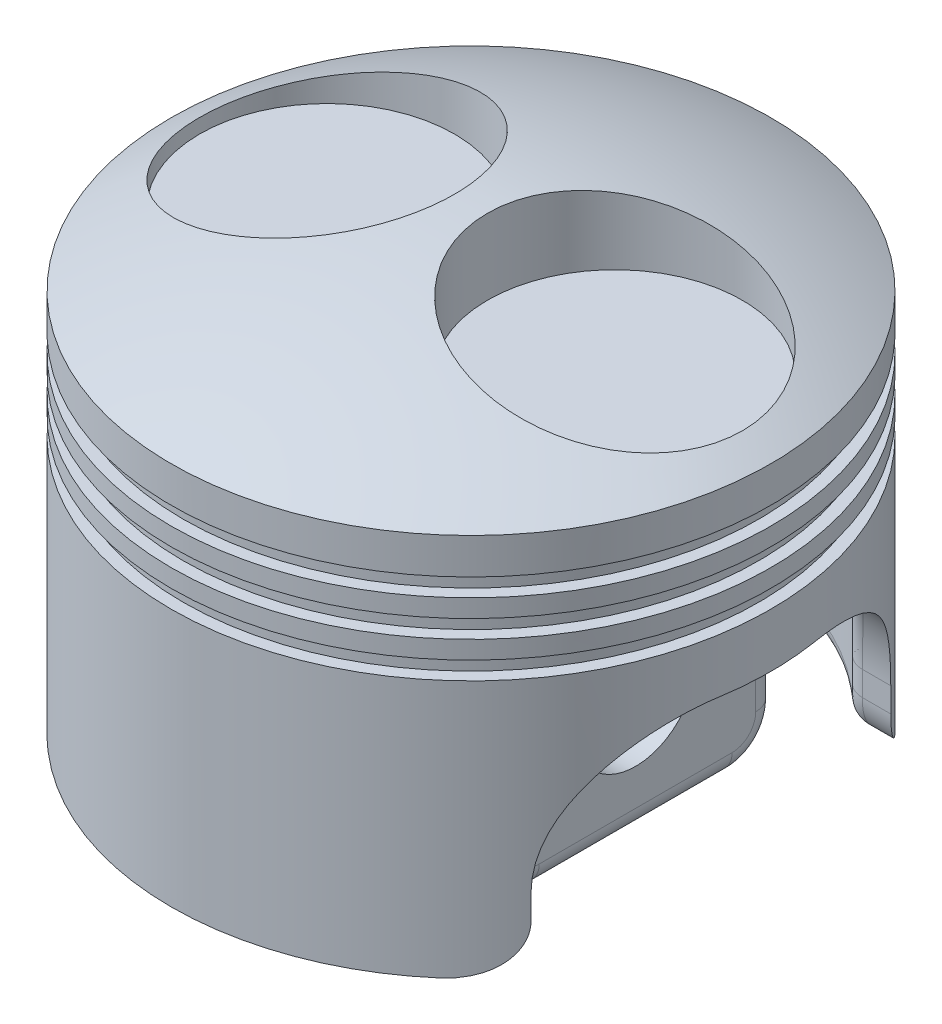
SolidWorks part; units mm, degrees
ref_plane "Front Plane" through (0, 0, 0) normal (0, 0, 1) x (1, 0, 0)
ref_plane "Top Plane" through (0, 0, 0) normal (0, 1, 0) x (1, 0, 0)
ref_plane "Right Plane" through (0, 0, 0) normal (1, 0, 0) x (0, 0, -1)
sketch "Sketch1" plane through (0, 0, 0) normal (0, 0, 1) x (1, 0, 0)
  line L0 (0, 0) -> (0, -19)
  line L1 (0, -19) -> (57.15, -19)
  line L2 (57.15, -19) -> (57.15, -81.28)
  line L3 (57.15, -81.28) -> (63.5, -81.28)
  line L4 (63.5, -81.28) -> (63.5, 0)
  line L5 (63.5, 0) -> (0, 0)
  dimension "D1" = 63.5
  dimension "D2" = 81.28
  dimension "D3" = 19
  dimension "D4" = 57.15
revolve "Revolve1" add sketch "Sketch1" angle 360 about L0
sketch "Sketch2" plane through (0, 0, 0) normal (1, 0, 0) x (0, 0, -1)
  line L0 (-63.5, -81.28) -> (63.5, -81.28) construction
  line L1 (-38.1, -38.1) -> (38.1, -38.1)
  line L2 (-38.1, -38.1) -> (-38.1, -81.28)
  line L3 (-38.1, -81.28) -> (38.1, -81.28)
  line L4 (38.1, -38.1) -> (38.1, -81.28)
  line L5 (-38.1, -38.1) -> (38.1, -81.28) construction
  line L6 (-38.1, -81.28) -> (38.1, -38.1) construction
  point P0 (0, -59.69)
  dimension "D1" = 76.2
  dimension "D2" = 43.18
extrude "Cut-Extrude1" cut sketch "Sketch2" against normal through all both and the other way through all
sketch "Sketch3" plane through (0, 0, 0) normal (1, 0, 0) x (0, 0, -1)
  line L0 (0, 0) -> (0, -31.9976) construction
  line L1 (63.5, -81.28) -> (63.5, 0) construction
  line L2 (60.96, -7.62) -> (66.04, -7.62)
  line L3 (60.96, -7.62) -> (60.96, -11.43)
  line L4 (60.96, -11.43) -> (66.04, -11.43)
  line L5 (66.04, -7.62) -> (66.04, -11.43)
  line L6 (60.96, -7.62) -> (66.04, -11.43) construction
  line L7 (60.96, -11.43) -> (66.04, -7.62) construction
  line L8 (63.5, 0) -> (-63.5, 0) construction
  point P3 (63.5, -9.525)
  dimension "D1" = 3.81
  dimension "D2" = 2.54
  dimension "D3" = 7.62
revolve "Cut-Revolve1" cut sketch "Sketch3" angle 360 about L0
pattern_linear "LPattern1" count 3 spacing 7.62 along (0, -1, 0) of "Cut-Revolve1"
sketch "Sketch4" plane through (0, -19, 0) normal (0, -1, 0) x (1, 0, 0)
  line L0 (0, 0) -> (0, 48.9565) construction
  line L1 (34.875, -30.43) -> (15.875, -30.43)
  line L2 (-34.875, 30.43) -> (-15.875, 30.43)
  line L3 (-34.875, 30.43) -> (-34.875, -30.43)
  line L4 (-34.875, -30.43) -> (-15.875, -30.43)
  line L5 (-15.875, 30.43) -> (-15.875, -30.43)
  line L6 (-34.875, 30.43) -> (-15.875, -30.43) construction
  line L7 (-34.875, -30.43) -> (-15.875, 30.43) construction
  line L8 (34.875, 30.43) -> (34.875, -30.43)
  line L9 (34.875, 30.43) -> (15.875, 30.43)
  line L10 (15.875, 30.43) -> (15.875, -30.43)
  point P3 (-25.375, 0)
  dimension "D1" = 19
  dimension "D2" = 60.86
  dimension "D3" = 31.75
extrude "Boss-Extrude1" add sketch "Sketch4" along normal blind 63.5
sketch "Sketch5" plane through (34.875, 0, 0) normal (1, 0, 0) x (0, 0, -1)
  line L0 (30.43, -82.5) -> (-30.43, -82.5) construction
  circle A0 centre (0, -57.1) radius 12.7
  dimension "D1" = 25.4
  dimension "D2" = 25.4
extrude "Cut-Extrude2" cut sketch "Sketch5" against normal through all and the other way through all
fillet "Fillet1" radius 28 4 edges at (46.6985, -38.1, -38.1) (46.6985, -38.1, 38.1) (-46.6985, -38.1, 38.1) (-46.6985, -38.1, -38.1)
fillet "Fillet2" radius 10 8 edges at (46.6985, -81.28, -38.1) (46.6985, -81.28, 38.1) (-46.6985, -81.28, 38.1) (-46.6985, -81.28, -38.1) (25.375, -82.5, -30.43) (25.375, -82.5, 30.43) (-25.375, -82.5, 30.43) (-25.375, -82.5, -30.43)
fillet "Fillet3" radius 5 16 edges at (40.0022, -78.1316, -40.816) (42.5971, -68.69, -38.1) (46.055, -51.2516, -33.8387) (57.15, -38.1, 0) (50.4318, -43.6881, 26.8841) (42.5971, -68.69, 38.1) (41.3657, -76.2692, 39.4335) (0, -81.28, 57.15) (-40.0022, -78.1316, 40.816) (-42.5971, -68.69, 38.1) (-46.055, -51.2516, 33.8387) (-57.15, -38.1, 0) (-50.4318, -43.6881, -26.8841) (-42.5971, -68.69, -38.1) (-41.3657, -76.2692, -39.4335) (0, -81.28, -57.15)
fillet "Fillet4" radius 5 20 edges at (-34.875, -45.75, 30.43) (-34.875, -79.5711, 27.5011) (-34.875, -45.75, -30.43) (-34.875, -79.5711, -27.5011) (-15.875, -45.75, -30.43) (-15.875, -79.5711, -27.5011) (-15.875, -45.75, 30.43) (-15.875, -79.5711, 27.5011) (15.875, -45.75, 30.43) (15.875, -79.5711, 27.5011) (15.875, -45.75, -30.43) (15.875, -79.5711, -27.5011) (34.875, -45.75, -30.43) (34.875, -79.5711, -27.5011) (34.875, -45.75, 30.43) (34.875, -79.5711, 27.5011) (-34.875, -82.5, 0) (-15.875, -82.5, 0) (15.875, -82.5, 0) (34.875, -82.5, 0)
fillet "Fillet5" radius 5 1 edges at (-57.15, -19, 0)
sketch "Sketch8" plane through (0, 0, 0) normal (0, 1, 0) x (1, 0, 0)
  circle A0 centre (30.48, 0) radius 27
  circle A1 centre (-30.48, 0) radius 27
  dimension "D2" = 54
  dimension "D4" = 54
dome "Dome3" faces to dome 1 distance 16 reverse direction no elliptical dome no face at (-63.5, 0, 0) parameters "D1"=16
extrude "Cut-Extrude6" cut sketch "Sketch8" along normal blind 20
